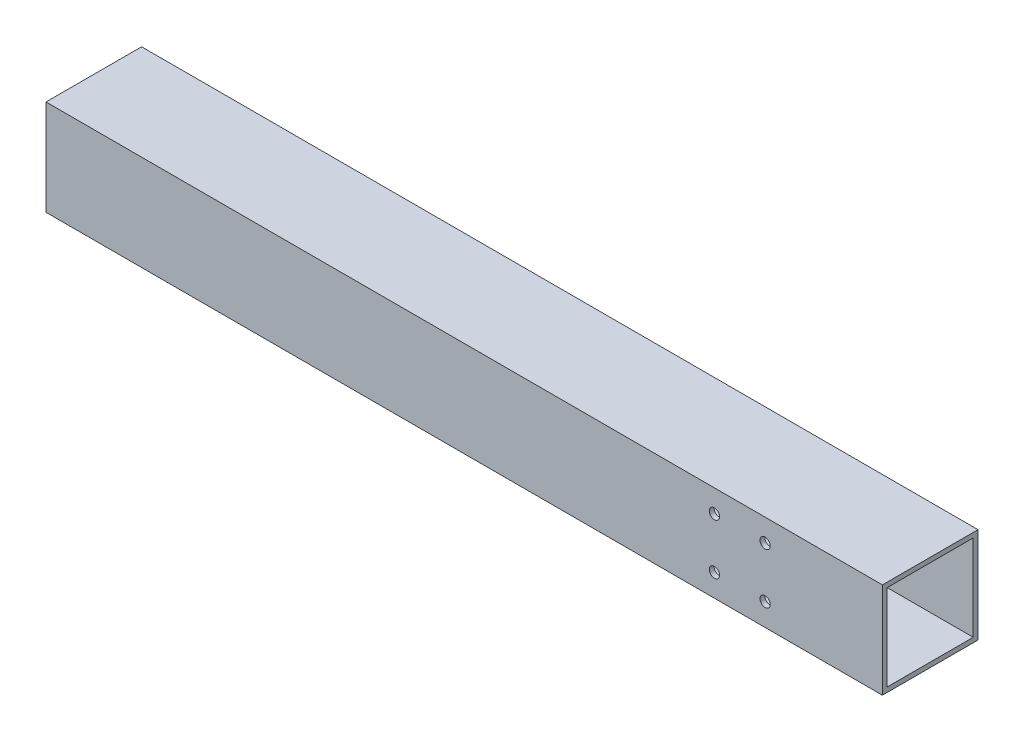
SolidWorks part; units mm, degrees
material "6061-T6 (SS)"
ref_plane "Front Plane" through (0, 0, 0) normal (0, 0, 1) x (1, 0, 0)
ref_plane "Top Plane" through (0, 0, 0) normal (0, 1, 0) x (1, 0, 0)
ref_plane "Right Plane" through (0, 0, 0) normal (1, 0, 0) x (0, 0, -1)
sketch "Sketch1" plane through (0, 0, 0) normal (1, 0, 0) x (0, 0, -1)
  line L0 (2, 2) -> (2, 38)
  line L1 (0, 0) -> (40, 0)
  line L2 (0, 0) -> (0, 40)
  line L3 (0, 40) -> (40, 40)
  line L4 (40, 0) -> (40, 40)
  line L5 (2, 38) -> (38, 38)
  line L6 (38, 2) -> (38, 38)
  line L7 (2, 2) -> (38, 2)
  dimension "D1" = 40
  dimension "D2" = 2
extrude "Boss-Extrude1" add sketch "Sketch1" along normal blind 350
sketch "Sketch2" plane through (0, 0, 0) normal (0, 0, 1) x (1, 0, 0)
  line L0 (350, 20) -> (290.313, 20) construction
  line L1 (350, 40) -> (350, 0) construction
  line L2 (290.313, 20) -> (300.9196, 30.6066)
  circle A0 centre (290.313, 20) radius 15 construction
  point P13 (300.9196, 30.6066)
  point P25 (300.9196, 9.3934)
  point P26 (279.7064, 9.3934)
  point P27 (279.7064, 30.6066)
  dimension "D1" = 30
  dimension "D2" = 4
hole_wizard "M4 Clearance Hole1" positions "Sketch2" profile "Sketch4" hole size "M4" standard "DIN"
sketch "Sketch4" plane through (279.7064, 30.6066, 0) normal (1, 0, 0) x (0, -1, 0)
  line L0 (0, 0) -> (0, 3.2919)
  line L1 (0, 3.2919) -> (2.15, 2)
  line L2 (2.15, 2) -> (2.15, 0)
  line L5 (2.15, 0) -> (0, 0)
  line L10 (0, 3.2919) -> (-2.15, 2) construction
  line L11 (0, -6.35) -> (0, 107.95) construction
  dimension "Hole Dia." = 4.3
  dimension "Hole Depth" = 2
  dimension "Drill Angle" = 118
sketch "Sketch5" plane through (0, 0, -40) normal (0, 0, -1) x (-1, 0, 0)
  line L0 (-350, 38) -> (0, 38) construction
  line L1 (-272.313, 2) -> (-308.313, 2) construction
  line L2 (-272.313, 2) -> (-272.313, 38) construction
  line L3 (-272.313, 38) -> (-308.313, 38) construction
  line L4 (-308.313, 2) -> (-308.313, 38) construction
  line L5 (-272.313, 2) -> (-308.313, 38) construction
  line L6 (-272.313, 38) -> (-308.313, 2) construction
  line L7 (-350, 38) -> (0, 38) construction
  line L8 (-350, 2) -> (0, 2) construction
  line L9 (-350, 2) -> (0, 2) construction
  line L10 (-272.813, 2.5) -> (-272.813, 37.5)
  line L11 (-272.813, 37.5) -> (-307.813, 37.5)
  line L12 (-307.813, 2.5) -> (-307.813, 37.5)
  line L13 (-272.813, 2.5) -> (-307.813, 2.5)
  circle A0 centre (-300.9196, 9.3934) radius 2.15 construction
  circle A1 centre (-279.7064, 9.3934) radius 2.15 construction
  circle A2 centre (-300.9196, 30.6066) radius 2.15 construction
  circle A3 centre (-279.7064, 30.6066) radius 2.15 construction
  circle A4 centre (-300.9196, 9.3934) radius 2.15 construction
  circle A5 centre (-279.7064, 9.3934) radius 2.15 construction
  circle A6 centre (-300.9196, 30.6066) radius 2.15 construction
  circle A7 centre (-279.7064, 30.6066) radius 2.15 construction
  circle A8 centre (-290.313, 20) radius 15 construction
  dimension "D1" = 0.5
extrude "Cut-Extrude1" cut sketch "Sketch5" against normal up to surface (2 mm away) up to face at (175, 20, -38)
